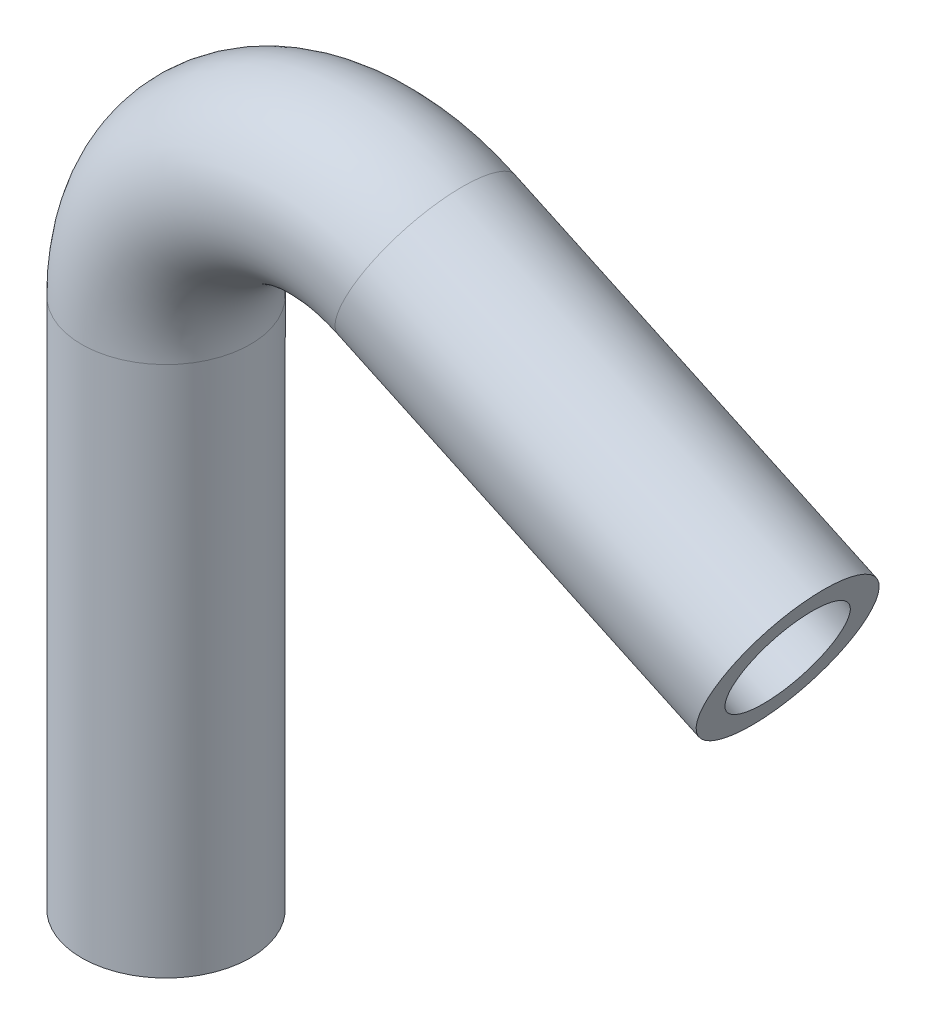
SolidWorks part; units mm, degrees
ref_plane "Piano frontale" through (0, 0, 0) normal (0, 0, 1) x (1, 0, 0)
ref_plane "Piano superiore" through (0, 0, 0) normal (0, 1, 0) x (1, 0, 0)
ref_plane "Piano destro" through (0, 0, 0) normal (1, 0, 0) x (0, 0, -1)
sketch "Schizzo1" plane through (0, 0, 0) normal (0, 0, 1) x (1, 0, 0)
  line L0 (0, 0) -> (0, 20)
  line L1 (9.8065, 26.2475) -> (23.4012, 19.9082)
  arc A0 (0, 20) -> (9.8065, 26.2475) centre (6.8933, 20) cw
  dimension "D1" = 15
  dimension "D2" = 20
  dimension "D3" = 65
sweep "Sweep-Sottile1" add path "Schizzo1" circular profile diameter 6.35 parameters "D1"=1, "D3"=6.35
